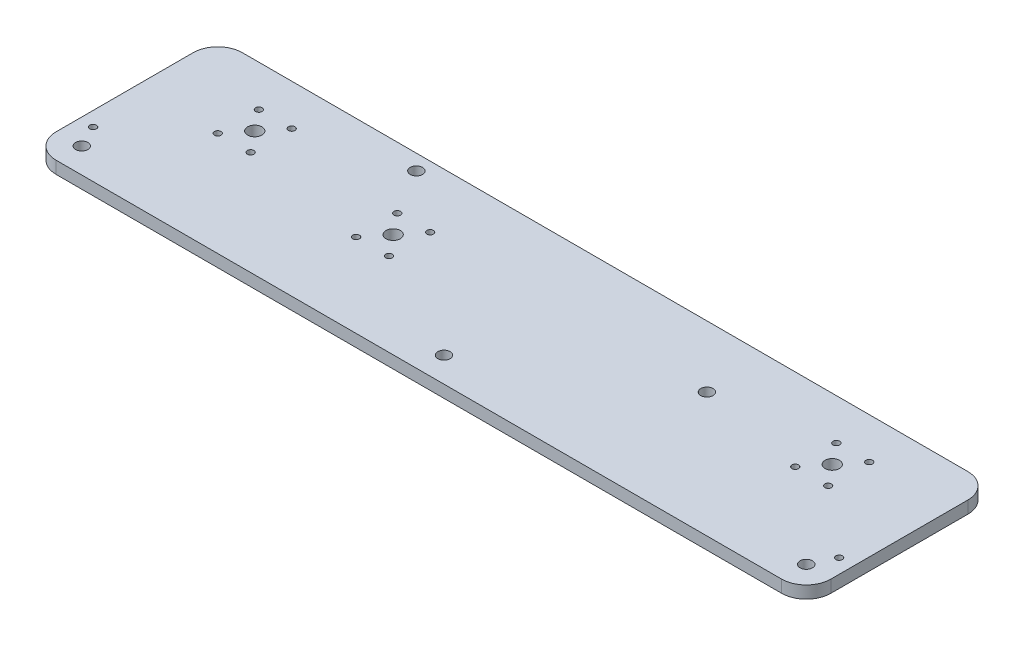
SolidWorks part; units mm, degrees
material "Policarbonato"
ref_plane "Plano frontal" through (0, 0, 0) normal (0, 0, 1) x (1, 0, 0)
ref_plane "Plano superior" through (0, 0, 0) normal (0, 1, 0) x (1, 0, 0)
ref_plane "Plano direito" through (0, 0, 0) normal (1, 0, 0) x (0, 0, -1)
sketch "Esboço1" plane through (0, 0, 0) normal (0, 1, 0) x (1, 0, 0)
  line L4 (132.965, 0) -> (148.965, 0) construction
  line L6 (188.965, -38.6487) -> (188.965, 28)
  line L7 (176.965, 40) -> (-176.0908, 40)
  line L8 (-188.0908, 28) -> (-188.0908, -38.6487)
  line L9 (132.965, 0) -> (132.965, 20) construction
  line L11 (132.965, 20) -> (148.965, 20) construction
  line L12 (148.965, 0) -> (148.965, 20) construction
  line L13 (132.965, 0) -> (148.965, 20) construction
  line L14 (132.965, 20) -> (148.965, 0) construction
  line L15 (-148.0908, 0) -> (-132.0908, 0) construction
  line L16 (-148.0908, 0) -> (-148.0908, 20) construction
  line L17 (-148.0908, 20) -> (-132.0908, 20) construction
  line L18 (-132.0908, 0) -> (-132.0908, 20) construction
  line L19 (-176.0908, -50.6487) -> (176.965, -50.6487)
  line L20 (-148.0908, 0) -> (-132.0908, 20) construction
  line L21 (-148.0908, 20) -> (-132.0908, 0) construction
  line L22 (-70.7345, -10) -> (-54.7345, -10) construction
  line L23 (-70.7345, -10) -> (-70.7345, 10) construction
  line L24 (-70.7345, 10) -> (-54.7345, 10) construction
  line L25 (-54.7345, -10) -> (-54.7345, 10) construction
  line L26 (-70.7345, -10) -> (-54.7345, 10) construction
  line L27 (-70.7345, 10) -> (-54.7345, -10) construction
  arc A0 (176.965, -50.6487) -> (188.965, -38.6487) centre (176.965, -38.6487) ccw
  arc A1 (188.965, 28) -> (176.965, 40) centre (176.965, 28) ccw
  arc A2 (-188.0908, 28) -> (-176.0908, 40) centre (-176.0908, 28) cw
  arc A3 (-188.0908, -38.6487) -> (-176.0908, -50.6487) centre (-176.0908, -38.6487) ccw
  circle A7 centre (-62.7345, 0) radius 3.5
  circle A8 centre (176.7481, -38.4318) radius 3
  circle A9 centre (0.4371, -38.4318) radius 3
  circle A10 centre (79.965, 10) radius 3
  circle A11 centre (-140.0908, 10) radius 3.5
  circle A13 centre (-148.0908, 0) radius 1.6
  circle A14 centre (-132.0908, 0) radius 1.6
  circle A15 centre (-132.0908, 20) radius 1.6
  circle A16 centre (-148.0908, 20) radius 1.6
  circle A17 centre (-70.7345, -10) radius 1.6
  circle A18 centre (-70.7345, 10) radius 1.6
  circle A19 centre (-54.7345, 10) radius 1.6
  circle A20 centre (-54.7345, -10) radius 1.6
  circle A21 centre (-62.7345, 0) radius 25 construction
  circle A22 centre (-83.9303, 32.5) radius 7.5 construction
  circle A23 centre (-140.0908, 10) radius 48 construction
  circle A24 centre (-83.9303, 32.5) radius 3
  circle A25 centre (-175.8739, -38.4318) radius 3
  circle A26 centre (140.965, 10) radius 3.5
  circle A27 centre (148.965, 0) radius 1.6
  circle A28 centre (148.965, 20) radius 1.6
  circle A29 centre (132.965, 0) radius 1.6
  circle A30 centre (132.965, 20) radius 1.6
  circle A33 centre (-181.0908, -27.6487) radius 1.6
  circle A34 centre (181.965, -27.6487) radius 1.6
  point P33 (0.4371, 40)
  point P41 (0, 0)
  dimension "D2" = 377.0558
  dimension "D4" = 7
  dimension "D6" = 12.2169
  dimension "D8" = 203.9448
  dimension "D10" = 48
  dimension "D12" = 16
  dimension "D15" = 20
  dimension "D17" = 6
  dimension "D1" = 12
  dimension "D7" = 40
  dimension "D9" = 30
  dimension "D11" = 7
  dimension "D16" = 3.2
  dimension "D20" = 3.2
  dimension "D25" = 56.1605
  dimension "D26" = 61
  dimension "D27" = 50
  dimension "D28" = 15
  dimension "D29" = 96
  dimension "D3" = 90.6487
  dimension "D5" = 12.2169
  dimension "D13" = 16
  dimension "D14" = 20
  dimension "D18" = 12.2169
  dimension "D19" = 30
  dimension "D21" = 16
  dimension "D22" = 20
  dimension "D23" = 48
  dimension "D24" = 7.5
  dimension "D30" = 7
  dimension "D31" = 7
  dimension "D32" = 23
extrude "Ressalto-extrusão1" add sketch "Esboço1" against normal blind 6
